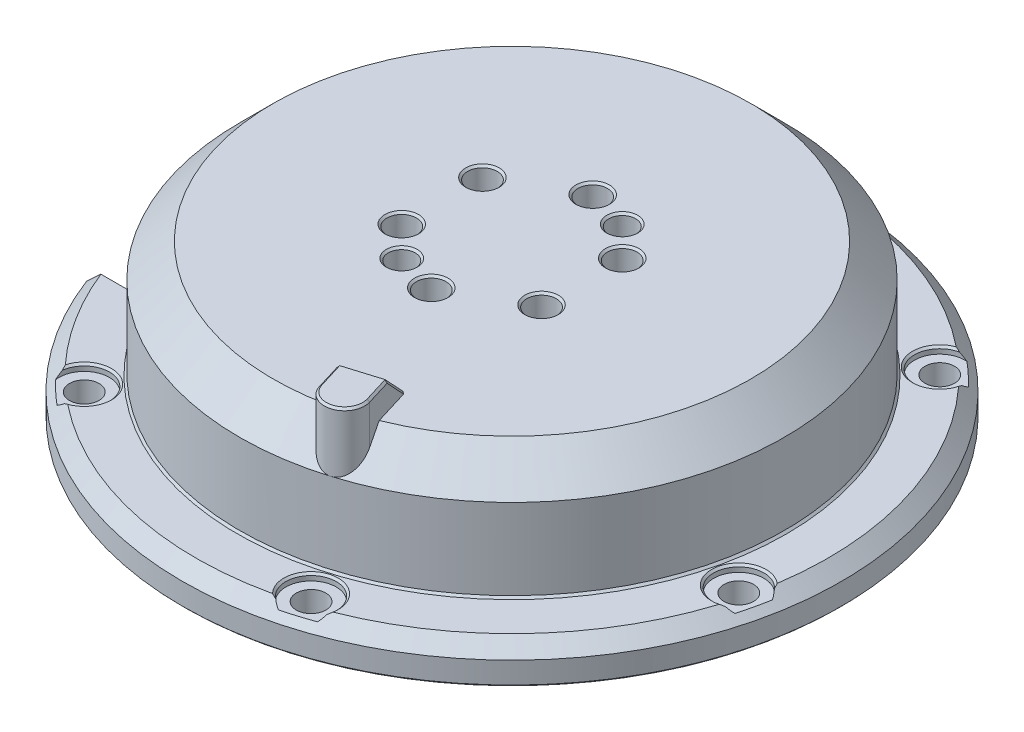
SolidWorks part; units mm, degrees
material "6061-T6 (SS)"
ref_plane "정면" through (0, 0, 0) normal (0, 0, 1) x (1, 0, 0)
ref_plane "윗면" through (0, 0, 0) normal (0, 1, 0) x (1, 0, 0)
ref_plane "우측면" through (0, 0, 0) normal (1, 0, 0) x (0, 0, -1)
sketch "스케치1" plane through (0, 0, 0) normal (0, 1, 0) x (1, 0, 0)
  circle A0 centre (0, 0) radius 49
  circle A1 centre (0, 0) radius 40.5
  circle A2 centre (0, 0) radius 36.5
  dimension "D1" = 98
  dimension "D2" = 81
  dimension "D3" = 73
extrude "보스-돌출1" add sketch "스케치1" along normal blind 5.5 contours A0 A1 region at (-47.6141, 0, 0)
extrude "보스-돌출2" add sketch "스케치1<5>" along normal blind 17.8 contours A1 A2 region at (-39.3545, 0, 0)
sketch "스케치1<5>" plane through (0, 0, 0) normal (0, 1, 0) x (1, 0, 0) same geometry as "스케치1"
extrude "보스-돌출3" add sketch "스케치1<6>" along normal blind 5 from surface contours A2 | A1 A2 region at (-39.3545, 0, 0) region at (0, 0, 0) starting at face at (0, 17.8, 36.5)
sketch "스케치1<6>" plane through (0, 0, 0) normal (0, 1, 0) x (1, 0, 0) same geometry as "스케치1"
sketch "스케치2" plane through (0, 22.8, 0) normal (0, 1, 0) x (1, 0, 0)
  line L0 (6, 10.3923) -> (-6, -10.3923) construction
  line L1 (0, 12) -> (0, 0) construction
  circle A0 centre (0, 0) radius 12
  circle A1 centre (0, 12) radius 2.2
  circle A2 centre (10.3923, 6) radius 2.2
  circle A3 centre (10.3923, -6) radius 2.2
  circle A4 centre (0, -12) radius 2.2
  circle A5 centre (-10.3923, -6) radius 2.2
  circle A6 centre (-10.3923, 6) radius 2.2
  circle A7 centre (6, 10.3923) radius 2
  circle A8 centre (-6, -10.3923) radius 2
  point P17 (0, 0)
  point P20 (0, 0)
  dimension "D1" = 24
  dimension "D2" = 4.4
  dimension "D4" = 4
  dimension "D5" = 30
  dimension "D3" = 6
extrude "컷-돌출1" cut sketch "스케치2" against normal blind 50 contours A0 A6 | A0 A6 | A0 A5 | A0 A5 | A0 A1 | A0 A1 | A0 A2 | A0 A2 | A0 A3 | A0 A3 | A0 A4 | A0 A4 region at (9.5531, 22.8, -5.5155) region at (11.1687, 22.8, -6.4482) region at (11.1687, 22.8, 6.4482) region at (9.5531, 22.8, 5.5155) region at (0, 22.8, 12.8964) region at (0, 22.8, 11.0309) region at (0, 22.8, -11.0309) region at (0, 22.8, -12.8964) region at (-9.5531, 22.8, -5.5155) region at (-11.1687, 22.8, -6.4482) region at (-11.1687, 22.8, 6.4482) region at (-9.5531, 22.8, 5.5155)
sketch "스케치3" plane through (0, 5.5, 0) normal (0, 1, 0) x (1, 0, 0)
  line L0 (-43.8467, 10.1228) -> (0, 0) construction
  line L1 (0, 0) -> (-45, 0) construction
  circle A0 centre (0, 0) radius 45
  circle A1 centre (-43.8467, 10.1228) radius 2.2
  circle A2 centre (-13.1567, 43.0337) radius 2.2
  circle A3 centre (30.6899, 32.9109) radius 2.2
  circle A4 centre (43.8467, -10.1228) radius 2.2
  circle A5 centre (13.1567, -43.0337) radius 2.2
  circle A6 centre (-30.6899, -32.9109) radius 2.2
  point P18 (0, 0)
  dimension "D1" = 90
  dimension "D2" = 4.4
  dimension "D3" = 13
  dimension "D4" = 6
extrude "컷-돌출2" cut sketch "스케치3" against normal blind 50 contours A0 A1 | A0 A1 | A0 A2 | A0 A2 | A0 A3 | A0 A3 | A0 A4 | A0 A4 | A0 A5 | A0 A5 | A0 A6 | A0 A6 region at (30.0466, 5.5, -32.221) region at (31.3201, 5.5, -33.5867) region at (44.7469, 5.5, 10.3306) region at (42.9275, 5.5, 9.9106) region at (-12.8809, 5.5, -42.1316) region at (-13.4269, 5.5, -43.9173) region at (13.4269, 5.5, 43.9173) region at (12.8809, 5.5, 42.1316) region at (-42.9275, 5.5, -9.9106) region at (-44.7469, 5.5, -10.3306) region at (-31.3201, 5.5, 33.5867) region at (-30.0466, 5.5, 32.221)
sketch "스케치4" plane through (0, 0, 0) normal (0, -1, 0) x (1, 0, 0)
  line L1 (-65.9688, 17.5) -> (-32.0312, 17.5)
  line L2 (-65.9688, 17.5) -> (-65.9688, -17.5)
  line L3 (-65.9688, -17.5) -> (-32.0312, -17.5)
  line L4 (-32.0312, 17.5) -> (-32.0312, -17.5)
  line L5 (-65.9688, 17.5) -> (-32.0312, -17.5) construction
  line L6 (-65.9688, -17.5) -> (-32.0312, 17.5) construction
  circle A0 centre (0, 0) radius 49 construction
  circle A1 centre (0, 0) radius 36.5 construction
  point P0 (-49, 0)
  dimension "D1" = 35
extrude "컷-돌출3" cut sketch "스케치4" against normal blind 11
sketch "스케치7" plane through (0, 5.5, 0) normal (0, 1, 0) x (1, 0, 0)
  line L0 (-13.1567, 43.0337) -> (0, 0) construction
  line L1 (0, 0) -> (30.6899, 32.9109) construction
  circle A0 centre (-13.1567, 43.0337) radius 3.75
  circle A1 centre (30.6899, 32.9109) radius 3.75
  circle A2 centre (43.8467, -10.1228) radius 3.75
  circle A3 centre (13.1567, -43.0337) radius 3.75
  circle A4 centre (-30.6899, -32.9109) radius 3.75
  circle A5 centre (-43.8467, 10.1228) radius 3.75
  point P15 (0, 0)
  dimension "D1" = 7.5
  dimension "D3" = 60
  dimension "D2" = 6
extrude "컷-돌출5" cut sketch "스케치7" against normal blind 1
chamfer "모따기8" distance 0.3 angle 45 7 edges at (0, 17.8, 36.5) (36.5, 0, 0) (49, 0, 0) (-34.2776, 11, 17.5) (-34.2776, 11, -17.5) (-38.8998, 0, 17.5) (-38.8998, 0, -17.5)
chamfer "모따기9" distance 2 angle 45 1 edges at (49, 5.5, 0)
sketch "스케치8" plane through (0, 22.8, 0) normal (0, 1, 0) x (1, 0, 0)
  line L0 (0, 0) -> (10.9639, -35.8614) construction
  line L1 (0, 0) -> (0, -40.5) construction
  line L2 (5.7561, -29.0881) -> (8.095, -36.7385)
  line L3 (11.4939, -27.3339) -> (13.8329, -34.9843)
  line L4 (5.7561, -29.0881) -> (11.4939, -27.3339)
  line L5 (8.095, -36.7385) -> (13.8329, -34.9843) construction
  circle A0 centre (10.9639, -35.8614) radius 3
  arc A3 (-36.524, -17.5) -> (-36.524, 17.5) centre (0, 0) ccw construction
  dimension "D3" = 6
  dimension "D1" = 8
  dimension "D2" = 17
chamfer "모따기11" distance 0.3 angle 45 1 edges at (40.5, 5.5, 0)
extrude "보스-돌출4" add sketch "스케치8" along normal blind 4 contours A0 | A0 L3 L4 L2 region at (9.4616, 22.8, 30.9476) region at (10.9639, 22.8, 35.8614)
chamfer "모따기12" distance 5 angle 45 1 edges at (0, 22.8, 40.5)
sketch "스케치10" plane through (-2.8689, 0, 0.8771) normal (-0.9563, 0, 0.2924) x (0.2924, 0, 0.9563)
  line L0 (29.5, 22.8) -> (33.5, 26.8)
  line L1 (29.5, 26.8) -> (37.5, 26.8) construction
  line L2 (33.5, 26.8) -> (29.5, 26.8)
  line L3 (29.5, 26.8) -> (29.5, 22.8)
extrude "컷-돌출8" cut sketch "스케치10" against normal blind 10
chamfer "모따기13" distance 0.3 angle 45 5 edges at (6.3408, 24.8, 31.0007) (12.0786, 24.8, 29.2465) (7.5103, 26.8, 34.8259) (11.8411, 26.8, 38.7303) (13.2481, 26.8, 33.0717)
extrude "컷-돌출9" cut sketch "스케치2<3>" against normal blind 4.5 contours A0 A7 | A0 A7 | A0 A8 | A0 A8 region at (5.5609, 22.8, -9.6318) region at (6.4091, 22.8, -11.1008) region at (-6.4091, 22.8, 11.1008) region at (-5.5609, 22.8, 9.6318)
sketch "스케치2<3>" plane through (0, 22.8, 0) normal (0, 1, 0) x (1, 0, 0) same geometry as "스케치2"
chamfer "모따기10" distance 0.3 angle 45 19 edges at (28.1324, 5.5, -30.1683) (40.1928, 5.5, 9.2792) (12.0603, 5.5, 39.4476) (-28.1324, 5.5, 30.1683) (-12.0603, 5.5, -39.4476) (0, 17.8, -9.8) (-10.3923, 17.8, -3.8) (-10.3923, 17.8, 8.2) (0, 17.8, 14.2) (10.3923, 17.8, -3.8) (10.3923, 17.8, 8.2) (0, 22.8, -9.8) (-10.3923, 22.8, -3.8) (-10.3923, 22.8, 8.2) (-6, 22.8, 12.3923) (0, 22.8, 14.2) (10.3923, 22.8, 8.2) (6, 22.8, -8.3923) (10.3923, 22.8, -3.8)
